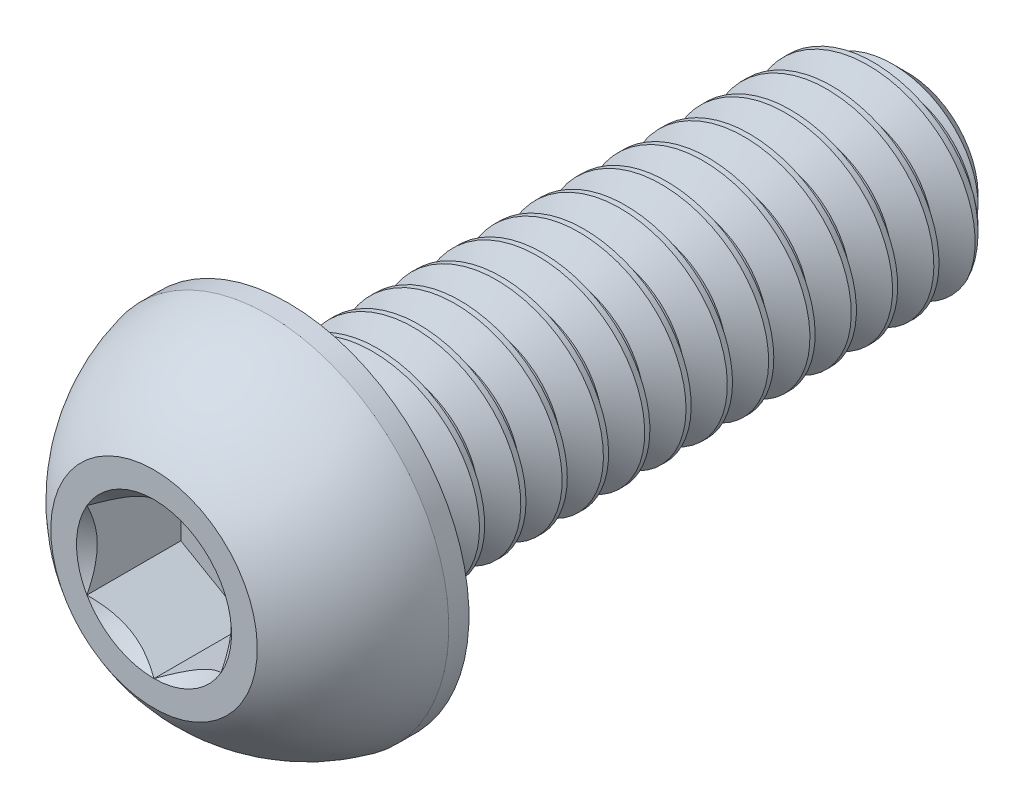
SolidWorks part; units mm, degrees
ref_plane "Front Plane" through (0, 0, 0) normal (0, 0, 1) x (1, 0, 0)
ref_plane "Top Plane" through (0, 0, 0) normal (0, 1, 0) x (1, 0, 0)
ref_plane "Right Plane" through (0, 0, 0) normal (1, 0, 0) x (0, 0, -1)
sketch "Sketch1" plane through (0, 0, 0) normal (1, 0, 0) x (0, 0, -1)
  line L0 (-3.65, 0) -> (3.65, 0) construction
  line L1 (-2.35, 1.75) -> (-2.35, -1.75) construction
  line L2 (3.65, 1) -> (3.65, -1) construction
  line L3 (3.625, 1.0433) -> (3.825, 0.6969) construction
  line L4 (3.825, 0.6969) -> (4.025, 1.0433) construction
  line L5 (4.025, 1.0433) -> (3.625, 1.0433) construction
  line L6 (3.65, 1) -> (4, 1) construction
  line L7 (3.825, 1.0433) -> (3.825, 1) construction
  line L8 (3.825, 1) -> (3.825, 0.7402) construction
  line L9 (3.825, 0.7402) -> (3.825, 0.6969) construction
  line L10 (3.8, 0.7402) -> (3.85, 0.7402)
  line L11 (3.6375, 1.0217) -> (4.0125, 1.0217)
  line L12 (3.85, 0.7402) -> (4.0125, 1.0217)
  line L13 (3.8, 0.7402) -> (3.6375, 1.0217)
  line L14 (-3.65, 0.65) -> (-3.65, -0.65) construction
  line L15 (3.65, 1) -> (-2.35, 1) construction
  point P3 (-2.35, 0)
  point P6 (-2.74, 0)
  point P21 (3.825, 1.0217)
  point P24 (-2.545, 1.75)
  point P25 (2.65, -1)
  point P26 (-3.65, 1)
  dimension "Head Height" = 1.3
  dimension "Length" = 6
  dimension "Head Dia" = 3.5
  dimension "Thread Dia" = 2
  dimension "Pitch" = 0.4
  dimension "D2" = 0.05
  dimension "Drive Size" = 1.3
  dimension "D1" = 0.91
  dimension "D3" = 0.195
  dimension "D4" = 1
sketch "Sketch2" plane through (0, 0, 0) normal (1, 0, 0) x (0, 0, -1)
  line L0 (-3.65, 0) -> (3.65, 0)
  line L1 (3.65, 0) -> (3.65, 0.68)
  line L2 (3.65, 1) -> (3.65, -1) construction
  line L3 (3.65, 0.68) -> (3.33, 1)
  line L4 (3.33, 1) -> (-2.35, 1)
  line L5 (-2.35, 1.75) -> (-2.35, -1.75) construction
  line L6 (-2.35, 1) -> (-2.35, 1.75)
  line L7 (-2.35, 1.75) -> (-2.545, 1.75)
  line L8 (3.65, 1) -> (4, 1) construction
  line L9 (-3.65, 0) -> (-3.65, 1)
  arc A0 (-3.65, 1) -> (-2.545, 1.75) centre (-2.1642, 0) cw
  dimension "D1" = 0.32
  dimension "D2" = 45
revolve "Revolve1" add sketch "Sketch2" angle 360 about L0
sketch "Sketch3" plane through (0, 0, 3.65) normal (0, 0, 1) x (1, 0, 0)
  line L1 (0, 0.7506) -> (-0.65, 0.3753)
  line L2 (-0.65, 0.3753) -> (-0.65, -0.3753)
  line L3 (-0.65, -0.3753) -> (0, -0.7506)
  line L4 (0, -0.7506) -> (0.65, -0.3753)
  line L5 (0.65, -0.3753) -> (0.65, 0.3753)
  line L6 (0.65, 0.3753) -> (0, 0.7506)
  circle A0 centre (0, 0) radius 0.65 construction
  dimension "D1" = 1.3
extrude "Cut-Extrude1" cut sketch "Sketch3" against normal up to vertex (0.91 mm away) up to point (0, 0, 2.74)
sketch "Sketch4" plane through (0, 0, 3.65) normal (0, 0, 1) x (1, 0, 0)
  circle A0 centre (0, 0) radius 0.7506
extrude "Cut-Extrude2" cut sketch "Sketch4" against normal blind 10 draft 45
split "Split1" bodies to split 106 resulting bodies 107 108 split by face at (0, -1.75, 2.35)
sketch "Sketch5" plane through (0, 0, -3.65) normal (0, 0, -1) x (-1, 0, 0)
  circle A0 centre (0, 0) radius 1 construction
  circle A1 centre (0, 0) radius 1
curve "Helix/Spiral1" pitch 0.4 height 6.4 radius 1 centre (0, 0, -3.65) axis (0, 0, 1) start towards (0, 1, 0)
sketch "Sketch6" plane through (0, 0, 0) normal (1, 0, 0) x (0, 0, -1)
  line L0 (3.8, 0.7402) -> (3.85, 0.7402) construction
  line L1 (3.8, 0.7402) -> (3.6375, 1.0217) construction
  line L2 (3.6375, 1.0217) -> (4.0125, 1.0217) construction
  line L3 (3.85, 0.7402) -> (4.0125, 1.0217) construction
  line L4 (3.8, 0.7402) -> (3.85, 0.7402)
  line L5 (3.8, 0.7402) -> (3.6375, 1.0217)
  line L6 (3.6375, 1.0217) -> (4.0125, 1.0217)
  line L7 (3.85, 0.7402) -> (4.0125, 1.0217)
sweep "Cut-Sweep1" cut profiles "Sketch6" path "Helix/Spiral1" align with end faces yes
sketch "Sketch7" plane through (0, 0, 2.35) normal (0, 0, -1) x (-1, 0, 0)
  circle A1 centre (0, 0) radius 1
  circle A2 centre (0, 0) radius 1
  dimension "D1" = 0
extrude "Boss-Extrude1" add sketch "Sketch7" along normal blind 10 draft 30
equation "\"D2@Sketch1\" = \"Pitch@Sketch1\" / 8"
equation "\"D1@Sketch1\"=\"Drive Size@Sketch1\"*.7"
equation "\"D3@Sketch1\"=\"Head Height@Sketch1\"*.15"
equation "\"D1@Sketch2\"=\"Pitch@Sketch1\"*.8"
equation "\"D1@Sketch3\"=\"Drive Size@Sketch1\""
equation "\"D4@Helix/Spiral1\"=\"Pitch@Sketch1\""
equation "\"D3@Helix/Spiral1\"=\"Length@Sketch1\"+\"Pitch@Sketch1\""
equation "\"D4@Sketch1\"=\"Pitch@Sketch1\"*2.5"
